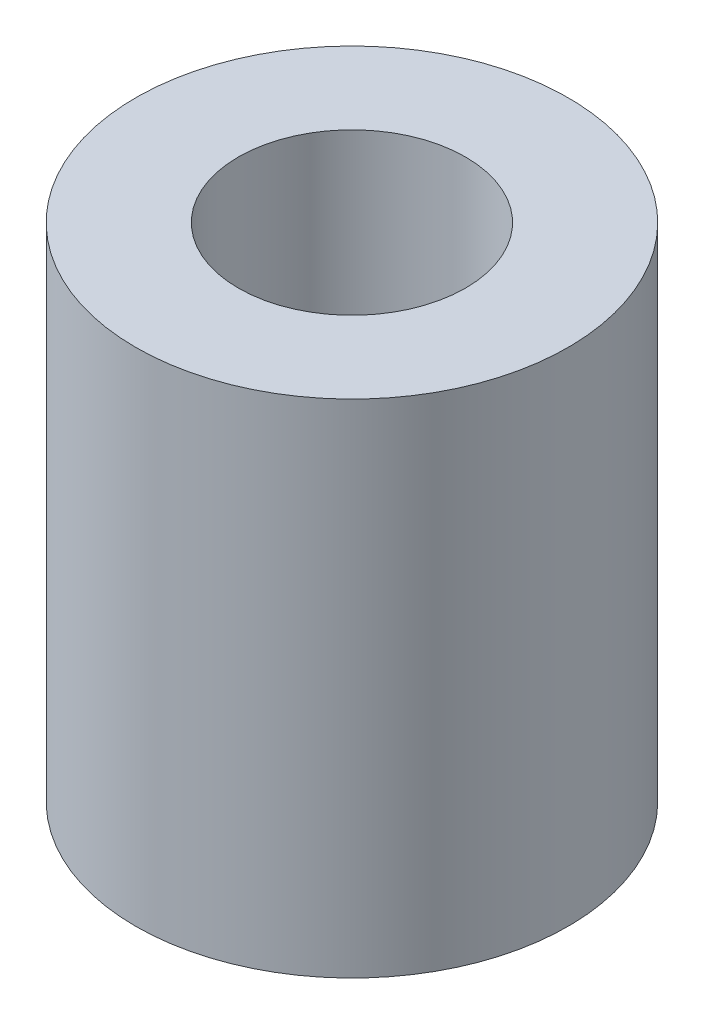
SolidWorks part; units mm, degrees
ref_plane "Front Plane" through (0, 0, 0) normal (0, 0, 1) x (1, 0, 0)
ref_plane "Top Plane" through (0, 0, 0) normal (0, 1, 0) x (1, 0, 0)
ref_plane "Right Plane" through (0, 0, 0) normal (1, 0, 0) x (0, 0, -1)
sketch "Sketch1" plane through (0, 0, 0) normal (0, 1, 0) x (1, 0, 0)
  circle A0 centre (0, 0) radius 6.9
  dimension "D1" = 13.8
extrude "Boss-Extrude1" add sketch "Sketch1" along normal blind 16
sketch "Sketch2" plane through (0, 16, 0) normal (0, 1, 0) x (1, 0, 0)
  circle A0 centre (0, 0) radius 3.625
  dimension "D1" = 7.25
extrude "Cut-Extrude1" cut sketch "Sketch2" against normal offset from surface (14 mm away) 2 up to face at (0, 0, 6.9)
